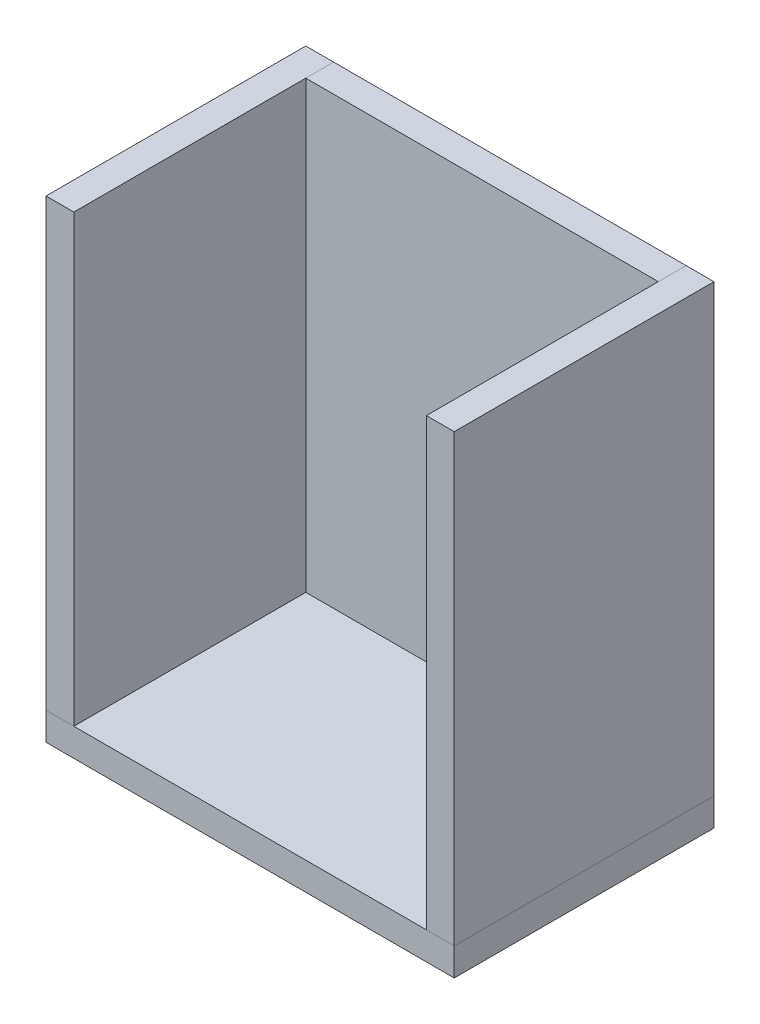
SolidWorks part; units mm, degrees
ref_plane "Front Plane" through (0, 0, 0) normal (0, 0, 1) x (1, 0, 0)
ref_plane "Top Plane" through (0, 0, 0) normal (0, 1, 0) x (1, 0, 0)
ref_plane "Right Plane" through (0, 0, 0) normal (1, 0, 0) x (0, 0, -1)
sketch "Sketch1" plane through (0, 0, 0) normal (0, 1, 0) x (1, 0, 0)
  line L1 (-139.7, 88.9) -> (139.7, 88.9)
  line L2 (-139.7, 88.9) -> (-139.7, -88.9)
  line L3 (-139.7, -88.9) -> (139.7, -88.9)
  line L4 (139.7, 88.9) -> (139.7, -88.9)
  line L5 (-139.7, 88.9) -> (139.7, -88.9) construction
  line L6 (-139.7, -88.9) -> (139.7, 88.9) construction
  point P0 (0, 0)
  dimension "D1" = 177.8
  dimension "D2" = 279.4
extrude "Boss-Extrude1" add sketch "Sketch1" along normal blind 19.05
sketch "Sketch2" plane through (0, 19.05, 0) normal (0, 1, 0) x (1, 0, 0)
  line L0 (-139.7, -88.9) -> (139.7, -88.9) construction
  line L1 (-139.7, 88.9) -> (-120.65, 88.9)
  line L2 (-139.7, 88.9) -> (-139.7, -88.9)
  line L3 (-139.7, -88.9) -> (-120.65, -88.9)
  line L4 (-120.65, 88.9) -> (-120.65, -88.9)
  line L6 (139.7, 88.9) -> (120.65, 88.9)
  line L7 (139.7, 88.9) -> (139.7, -88.9)
  line L8 (139.7, -88.9) -> (120.65, -88.9)
  line L9 (120.65, 88.9) -> (120.65, -88.9)
  line L10 (-120.65, 88.9) -> (120.65, 88.9)
  line L11 (-120.65, 88.9) -> (-120.65, 69.85)
  line L12 (-120.65, 69.85) -> (120.65, 69.85)
  line L13 (120.65, 88.9) -> (120.65, 69.85)
  line M7 (139.7, -88.9) -> (139.7, 88.9)
  line M8 (139.7, 88.9) -> (-139.7, 88.9)
  line M9 (-139.7, 88.9) -> (-139.7, -88.9)
  line M10 (-139.7, -88.9) -> (139.7, -88.9)
  dimension "D1" = 19.05
  dimension "D2" = 19.05
  dimension "D3" = 19.05
extrude "Boss-Extrude2" add sketch "Sketch2" along normal blind 304.8 separate body contours L4 M8 M9 M10 | L9 M8 M10 M7 region at (-130.175, 19.05, 0) region at (130.175, 19.05, 0)
extrude "Boss-Extrude3" add sketch "Sketch2<3>" along normal up to surface (304.8 mm away) separate body contours L4 L12 L9 M8 region at (0, 19.05, -79.375) up to face at (-130.175, 323.85, 0)
sketch "Sketch2<3>" plane through (0, 19.05, 0) normal (0, 1, 0) x (1, 0, 0) same geometry as "Sketch2"
